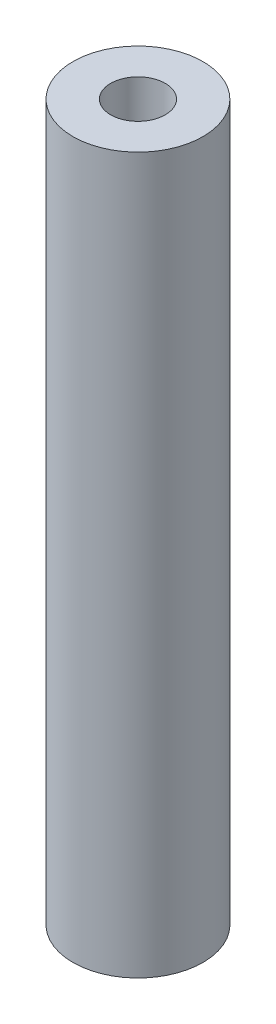
SolidWorks part; units mm, degrees
ref_plane "Front Plane" through (0, 0, 0) normal (0, 0, 1) x (1, 0, 0)
ref_plane "Top Plane" through (0, 0, 0) normal (0, 1, 0) x (1, 0, 0)
ref_plane "Right Plane" through (0, 0, 0) normal (1, 0, 0) x (0, 0, -1)
sketch "Sketch1" plane through (0, 0, 0) normal (0, 1, 0) x (1, 0, 0)
  circle A0 centre (0, 0) radius 6.35
  circle A1 centre (0, 0) radius 2.667
  dimension "D1" = 12.7
  dimension "D2" = 5.334
extrude "Boss-Extrude1" add sketch "Sketch1" along normal blind 69.85
sketch "Sketch2" plane through (0, 0, 0) normal (0, -1, 0) x (-1, 0, 0)
  circle A0 centre (0, 0) radius 9.525
  circle A1 centre (0, 0) radius 2.54
  dimension "D1" = 19.05
extrude "Boss-Extrude2" [suppressed] add sketch "Sketch2" against normal blind 7.62
chamfer "Chamfer1" [suppressed] distance 3.175 angle 68
fillet "Fillet1" [suppressed] radius 12.7
sketch "Sketch3" plane through (0, 69.85, 0) normal (0, 1, 0) x (1, 0, 0)
  circle A0 centre (0, 0) radius 9.525
  circle A1 centre (0, 0) radius 2.54
  dimension "D1" = 19.05
extrude "Boss-Extrude3" [suppressed] add sketch "Sketch3" against normal blind 7.62
chamfer "Chamfer2" [suppressed] distance 3.175 angle 68
fillet "Fillet2" [suppressed] radius 12.7
sketch "Sketch4" plane through (0, 0, 0) normal (0, 0, 1) x (1, 0, 0)
  line L1 (-14.5993, 37.9681) -> (14.5993, 37.9681)
  line L2 (-14.5993, 37.9681) -> (-14.5993, -4.7123)
  line L3 (-14.5993, -4.7123) -> (14.5993, -4.7123)
  line L4 (14.5993, 37.9681) -> (14.5993, -4.7123)
  line L5 (-14.5993, 37.9681) -> (14.5993, -4.7123) construction
  line L6 (-14.5993, -4.7123) -> (14.5993, 37.9681) construction
  point P0 (0, 16.6279)
extrude "Cut-Extrude1" [suppressed] cut sketch "Sketch4" along normal through all from offset 6.35
